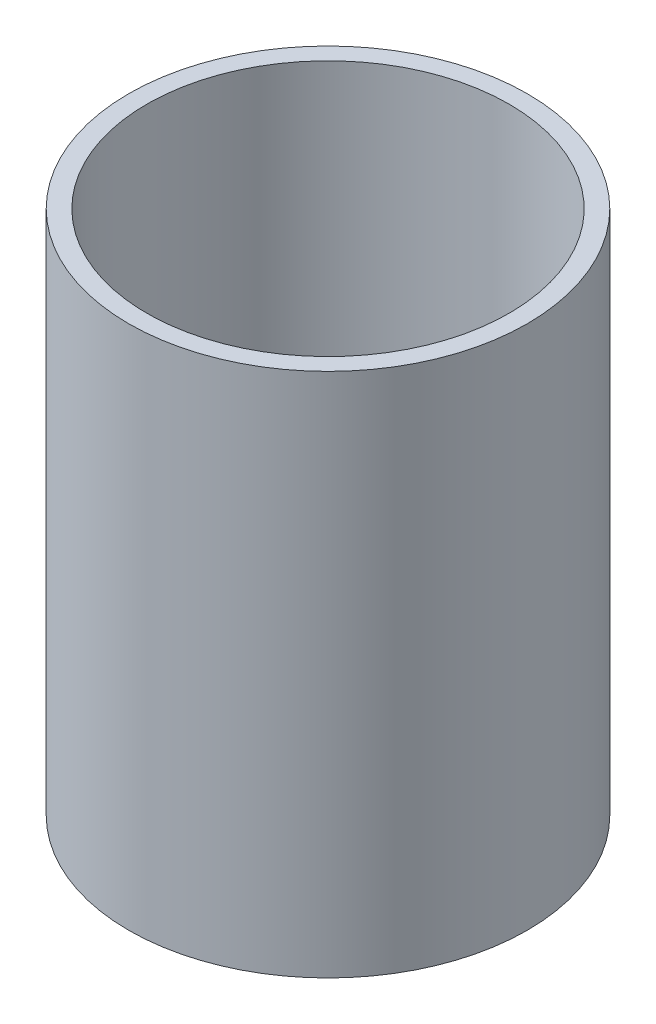
SolidWorks part; units mm, degrees
ref_plane "Front" through (0, 0, 0) normal (0, 0, 1) x (1, 0, 0)
ref_plane "Top" through (0, 0, 0) normal (0, 1, 0) x (1, 0, 0)
ref_plane "Right" through (0, 0, 0) normal (1, 0, 0) x (0, 0, -1)
sketch "Sketch1" plane through (0, 0, 0) normal (0, 1, 0) x (1, 0, 0)
  circle A0 centre (0, 0) radius 11
  circle A1 centre (0, 0) radius 10
  dimension "D1" = 20
  dimension "D2" = 22
extrude "Boss-Extrude1" add sketch "Sketch1" along normal blind 29
